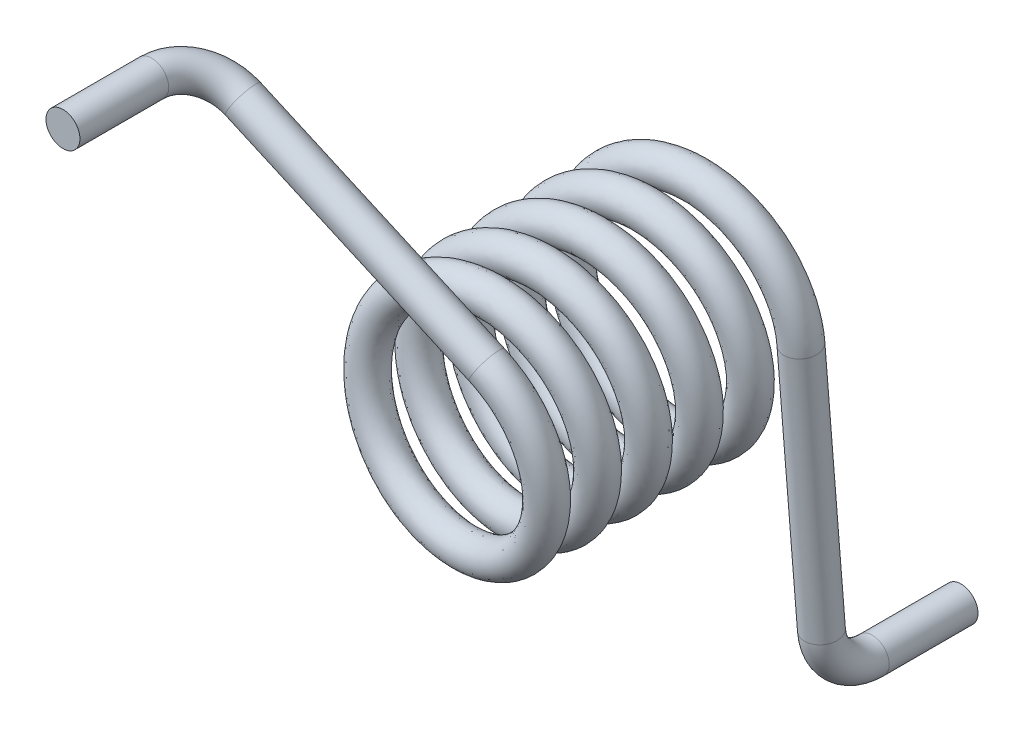
SolidWorks part; units mm, degrees
ref_plane "前视基准面" through (0, 0, 0) normal (0, 0, 1) x (1, 0, 0)
ref_plane "上视基准面" through (0, 0, 0) normal (0, 1, 0) x (1, 0, 0)
ref_plane "右视基准面" through (0, 0, 0) normal (1, 0, 0) x (0, 0, -1)
sketch "草图1" plane through (0, 0, 0) normal (0, 0, 1) x (1, 0, 0)
  circle A0 centre (0, 0) radius 6
  dimension "D1" = 12
curve "扭簧" pitch 3 height 15.5 turns 5.1667
ref_plane "基准面1" through (9, 0, 0) normal (1, 0, 0) x (0, 0, -1)
sketch "草图2" plane through (9, 0, 0) normal (1, 0, 0) x (0, 0, -1)
  line L0 (0, 0) -> (1.9448, -14.0028)
sketch "草图3" plane through (0, 0, 0) normal (0, 1, 0) x (1, 0, 0)
  line L0 (0, 0) -> (0, 30) construction
ref_plane "基准面2" through (0, 0, 0) normal (-0.5, -0.866, 0) x (-0.866, 0.5, 0)
ref_plane "基准面3" through (4.5, 7.7942, 0) normal (-0.5, -0.866, 0) x (-0.866, 0.5, 0)
sketch "草图4" plane through (4.5, 7.7942, 0) normal (-0.5, -0.866, 0) x (-0.866, 0.5, 0)
  line L0 (0, -15.8333) -> (14.0028, -17.7782)
ref_plane "基准面4" through (-7.6267, 14.7956, 17.7782) normal (-0.8578, 0.4952, 0.1376) x (0.1191, -0.0688, 0.9905)
sweep "扫描2" add path "扭簧" circular profile diameter 2 parameters "D3"=2
sketch3d "3D草图2"
  line L0 (3, 5.1962, 15.5) -> (-12.5392, 14.1679, 16.9279)
  line L1 (0, 0, 0) -> (0, 18.4611, 0) construction
  spline S0 degree 3 poles (6, 0, 0) (6, 0.7867, 0.0626) (5.6824, 2.3773, 0.1892) (4.327, 4.382, 0.378) (2.3023, 5.7125, 0.5671) (-0.0786, 6.1582, 0.7561) (-2.4474, 5.6516, 0.9451) (-4.4375, 4.2707, 1.1341) (-5.7412, 2.2291, 1.3232) (-6.1568, -0.1573, 1.5122) (-5.6199, -2.5194, 1.7012) (-4.2137, -4.4917, 1.8902) (-2.1556, -5.7692, 2.0793) (0.2359, -6.1543, 2.2683) (2.5909, -5.5873, 2.4573) (4.5452, -4.156, 2.6463) (5.7963, -2.0818, 2.8354) (6.1508, 0.3145, 3.0244) (5.5537, 2.6621, 3.2134) (4.0976, 4.5979, 3.4024) (2.0076, 5.8224, 3.5915) (-0.393, 6.1462, 3.7805) (-2.7328, 5.5193, 3.9695) (-4.6498, 4.0385, 4.1585) (-5.8476, 1.9331, 4.3476) (-6.1407, -0.4715, 4.5366) (-5.4839, -2.803, 4.7256) (-3.9788, -4.701, 4.9146) (-1.8582, -5.8718, 5.1037) (0.5498, -6.1342, 5.2927) (2.8728, -5.4477, 5.4817) (4.7514, -3.9185, 5.6707) (5.895, -1.7831, 5.8598) (6.1267, 0.6281, 6.0488) (5.4106, 2.9422, 6.2378) (3.8575, 4.8011, 6.4268) (1.7077, 5.9173, 6.6159) (-0.7063, 6.1182, 6.8049) (-3.011, 5.3726, 6.9939) (-4.85, 3.7959, 7.1829) (-5.9386, 1.632, 7.372) (-6.1086, -0.7844, 7.561) (-5.3337, -3.0794, 7.75) (-3.7336, -4.898, 7.939) (-1.556, -5.959, 8.128) (0.8623, -6.0981, 8.3171) (3.1473, -5.2939, 8.5061) (4.9453, -3.6708, 8.6951) (5.9784, -1.4798, 8.8841) (6.0866, 0.9401, 9.0732) (5.2533, 3.2146, 9.2622) (3.6073, 4.9918, 9.4512) (1.4033, 5.9968, 9.6402) (-1.0178, 6.0741, 9.8293) (-3.2814, 5.2118, 10.0183) (-5.0375, 3.5433, 10.2073) (-6.0142, 1.3266, 10.3963) (-6.0606, -1.0953, 10.5854) (-5.1695, -3.3477, 10.7744) (-3.4786, -5.0823, 10.9634) (-1.2497, -6.0307, 11.1524) (1.1726, -6.0461, 11.3415) (3.4135, -5.1263, 11.5305) (5.1263, -3.4135, 11.7195) (6.0461, -1.1726, 11.9085) (6.0307, 1.2497, 12.0976) (5.0823, 3.4786, 12.2866) (3.3477, 5.1695, 12.4756) (1.0953, 6.0606, 12.6646) (-1.3266, 6.0142, 12.8537) (-3.5433, 5.0375, 13.0427) (-5.2118, 3.2814, 13.2317) (-6.0741, 1.0178, 13.4207) (-5.9968, -1.4033, 13.6098) (-4.9918, -3.6073, 13.7988) (-3.2146, -5.2533, 13.9878) (-0.9401, -6.0866, 14.1768) (1.4798, -5.9784, 14.3659) (3.6708, -4.9453, 14.5549) (5.2939, -3.1472, 14.7439) (6.0983, -0.8624, 14.9329) (5.9584, 1.5563, 15.122) (4.9001, 3.7324, 15.3108) (3.6813, 4.8028, 15.4374) (3, 5.1962, 15.5) knots 0 0 0 0 0.012195 0.02439 0.036585 0.04878 0.060976 0.073171 0.085366 0.097561 0.109756 0.121951 0.134146 0.146341 0.158537 0.170732 0.182927 0.195122 0.207317 0.219512 0.231707 0.243902 0.256098 0.268293 0.280488 0.292683 0.304878 0.317073 0.329268 0.341463 0.353659 0.365854 0.378049 0.390244 0.402439 0.414634 0.426829 0.439024 0.45122 0.463415 0.47561 0.487805 0.5 0.512195 0.52439 0.536585 0.54878 0.560976 0.573171 0.585366 0.597561 0.609756 0.621951 0.634146 0.646341 0.658537 0.670732 0.682927 0.695122 0.707317 0.719512 0.731707 0.743902 0.756098 0.768293 0.780488 0.792683 0.804878 0.817073 0.829268 0.841463 0.853659 0.865854 0.878049 0.890244 0.902439 0.914634 0.926829 0.939024 0.95122 0.963415 0.97561 0.987805 1 1 1 1 construction
  dimension "D1" = 18
ref_plane "基准面5" through (1.4375, 0, 15.6436) normal (-0.0915, 0, -0.9958) x (-0.8633, 0.4984, 0.0793)
ref_plane "基准面6" through (3.0001, 5.1961, 0) normal (0.5, 0.866, 0) x (-0.8633, 0.4984, 0.0793)
sketch "草图55" plane through (0, 0, 0) normal (0, 1, 0) x (1, 0, 0)
  line L0 (0, 0) -> (0, -16.1332) construction
sketch "草图54" plane through (3.0001, 5.1961, 0) normal (0.5, 0.866, 0) x (-0.8633, 0.4984, 0.0793)
  line L0 (19.4494, 18.2132) -> (19.8642, 23.4259)
  line L1 (0, 0) -> (1.2798, 16.0824) construction
  line L2 (0, 0) -> (1.2798, 16.0824) construction
  line L3 (1.2296, 15.4511) -> (19.2296, 15.4511) construction
  line L4 (1.2296, 15.4511) -> (16.4589, 15.4511)
  arc A0 (16.4589, 15.4511) -> (19.4494, 18.2132) centre (16.4589, 18.4511) ccw
  point P9 (19.2296, 15.4511)
  dimension "D1" = 3
  dimension "D2" = 8
sweep "扫描4" add path "草图54" circular profile diameter 2 parameters "D3"=2
sketch3d "3D草图3"
  line L0 (6, 0, 0) -> (6, -17.9433, -1.4279)
  circle A0 centre (6, 0, 0) radius 1 construction
  point P6 (6, 0.9968, 0.0793)
  dimension "D1" = 18
ref_plane "基准面7" through (6, 0, 0) normal (-1, 0, 0) x (0, -0.9968, -0.0793)
sketch "草图97" plane through (6, 0, 0) normal (-1, 0, 0) x (0, -0.9968, -0.0793)
  line L0 (0, 0) -> (18, 0) construction
  line L1 (0, 0) -> (15.2292, 0)
  line L2 (0, 0) -> (-1.2798, 16.0824) construction
  line L3 (0, 0) -> (-1.2798, 16.0824) construction
  line L4 (18.2198, -2.762) -> (18.6346, -7.9748)
  arc A0 (18.2198, -2.762) -> (15.2292, 0) centre (15.2292, -3) ccw
  point P7 (18, 0)
  dimension "D1" = 3
  dimension "D2" = 8
sweep "扫描5" add path "草图97" circular profile diameter 2 parameters "D3"=2
sketch "参数说明" plane through (0, 0, 0) normal (1, 0, 0) x (0, 0, -1)
  line L0 (34.9766, -5.831) -> (34.9766, -25)
  line L1 (-50.9722, 18.8612) -> (-45.7722, 18.8612)
  line L2 (36.9766, -25) -> (36.9766, 0)
  line L3 (32.2266, 8.2272) -> (10.576, 20.7272)
  line L4 (-44.7746, 17.9301) -> (-42.9447, -8.5689)
  line L5 (9.576, 18.9952) -> (31.2266, 6.4952)
  line L6 (-50.9722, 18.8612) -> (-50.9722, 20.8612)
  line L7 (-50.9722, 20.8612) -> (-45.7722, 20.8612)
  line L8 (-42.7793, 18.0679) -> (-40.9494, -8.4311)
  line L9 (-41.5482, 7.5869) -> (-41.8313, 4.3395)
  line L10 (-40.6677, -5.3395) -> (-40.9508, -8.5869)
  line L14 (-39.5543, 7.5689) -> (-38.4494, -8.4311)
  line L15 (-41.5496, 7.4311) -> (-40.4447, -8.5689)
  line L16 (-41.9471, -8.5) -> (-39.4471, -8.5) construction
  line L17 (-39.4471, -8.5) -> (-36.9471, -8.5) construction
  line L18 (-36.9471, -8.5) -> (-34.4471, -8.5) construction
  line L19 (-40.5519, 7.5) -> (-38.0519, 7.5) construction
  line L20 (-38.0519, 7.5) -> (-35.5519, 7.5) construction
  line L21 (-35.5519, 7.5) -> (-33.0519, 7.5) construction
  line L22 (-33.0519, 7.5) -> (-30.5519, 7.5) construction
  line L23 (-39.3313, 4.3395) -> (-39.0482, 7.5869)
  line L24 (-38.1677, -5.3395) -> (-38.4508, -8.5869)
  line L25 (-34.4471, -8.5) -> (-31.9471, -8.5) construction
  line L26 (-39.0496, 7.4311) -> (-37.9447, -8.5689)
  line L27 (-37.0543, 7.5689) -> (-35.9494, -8.4311)
  line L28 (-36.5496, 7.4311) -> (-35.4447, -8.5689)
  line L29 (-34.5543, 7.5689) -> (-33.4494, -8.4311)
  line L30 (-34.0496, 7.4311) -> (-32.9447, -8.5689)
  line L31 (-32.0543, 7.5689) -> (-30.9494, -8.4311)
  line L32 (8.4616, 20.7933) -> (31.7266, 7.3612) construction
  line L33 (10.576, 20.7272) -> (9.0021, 18.0012) construction
  line L34 (-34.0482, 7.5869) -> (-34.3313, 4.3395)
  line L35 (-31.5496, 7.4311) -> (-29.4339, -23.2067)
  line L36 (-36.8313, 4.3395) -> (-36.5482, 7.5869)
  line L37 (-35.6677, -5.3395) -> (-35.9508, -8.5869)
  line L38 (-31.8313, 4.3395) -> (-31.5482, 7.5869)
  line L39 (-33.1677, -5.3395) -> (-33.4508, -8.5869)
  line L40 (-26.441, -26) -> (-21.241, -26)
  line L41 (-21.241, -26) -> (-21.241, -24)
  line L42 (-21.241, -24) -> (-26.441, -24)
  line L43 (-27.4386, -23.0689) -> (-29.5543, 7.5689)
  line L44 (-30.6677, -5.3395) -> (-30.9508, -8.5869)
  line L45 (35.9766, 0) -> (35.9766, -27.1739) construction
  circle A0 centre (27.4766, 0) radius 7.5
  arc A1 (26.1768, 9.4107) -> (32.2266, 8.2272) centre (27.4766, 0) ccw
  arc A2 (34.9766, -25) -> (36.9766, -25) centre (35.9766, -25) ccw
  circle A4 centre (10.076, 19.8612) radius 1
  arc A5 (-42.9447, -8.5689) -> (-40.9494, -8.4311) centre (-41.9471, -8.5) ccw
  arc A6 (-39.5543, 7.5689) -> (-41.5496, 7.4311) centre (-40.5519, 7.5) ccw
  circle A7 centre (27.4766, 0) radius 8.5 construction
  arc A8 (-40.4447, -8.5689) -> (-38.4494, -8.4311) centre (-39.4471, -8.5) ccw
  arc A9 (-37.0543, 7.5689) -> (-39.0496, 7.4311) centre (-38.0519, 7.5) ccw
  arc A10 (-34.5543, 7.5689) -> (-36.5496, 7.4311) centre (-35.5519, 7.5) ccw
  arc A11 (-32.0543, 7.5689) -> (-34.0496, 7.4311) centre (-33.0519, 7.5) ccw
  arc A12 (-37.9447, -8.5689) -> (-35.9494, -8.4311) centre (-36.9471, -8.5) ccw
  arc A13 (-35.4447, -8.5689) -> (-33.4494, -8.4311) centre (-34.4471, -8.5) ccw
  arc A14 (-32.9447, -8.5689) -> (-30.9494, -8.4311) centre (-31.9471, -8.5) ccw
  arc A15 (-29.5543, 7.5689) -> (-31.5496, 7.4311) centre (-30.5519, 7.5) ccw
  arc A16 (-44.7746, 17.9301) -> (-45.7722, 18.8612) centre (-45.7722, 17.8612) ccw
  arc A18 (-42.7793, 18.0679) -> (-45.7722, 20.8612) centre (-45.7722, 17.8612) ccw
  arc A19 (-27.4386, -23.0689) -> (-26.441, -24) centre (-26.441, -23) ccw
  arc A21 (-29.4339, -23.2067) -> (-26.441, -26) centre (-26.441, -23) ccw
  point P54 (-42.9722, 20.8612)
  dimension "D2" = 120
  dimension "D6" = 16
  dimension "D11" = 1
  dimension "D4" = 25
  dimension "D5" = 8
  dimension "D7" = 2.5
  dimension "D9" = 2
equation "\"d\"= 2'线径（弹簧丝直径）"
equation "\"D1\"= 12'中径"
equation "\"q\"= 3'节距"
equation "\"n\"= 5'有效圈数"
equation "\"θ\"= 120'展开角"
equation "\"D3@扫描2\"= \"d\"'注意：此弹簧为右旋"
equation "\"D4@扭簧\"= \"q\" '各变量含义可在设计树”参数说明”查看"
equation "\"D5@扭簧\" = \"n\" + ( ( 180 - \"θ\" ) / 360 )"
equation "\"D1@3D草图2\"= \"L\""
equation "\"D1@草图1\"=\"D1\""
equation "\"D1@3D草图3\"=\"L\""
equation "\"L\"= 18'扭转臂长度"
equation "\"J\"= 8'折弯长度"
equation "\"R\"= 2'折弯半径"
equation "\"D3@扫描4\"=\"d\""
equation "\"D3@扫描5\"=\"d\""
equation "\"D2@草图54\"=\"J\""
equation "\"D2@草图97\"=\"J\""
equation "\"D1@草图97\"=\"R\"+\"d\"/2"
equation "\"D1@草图54\"=\"R\"+\"d\"/2"
